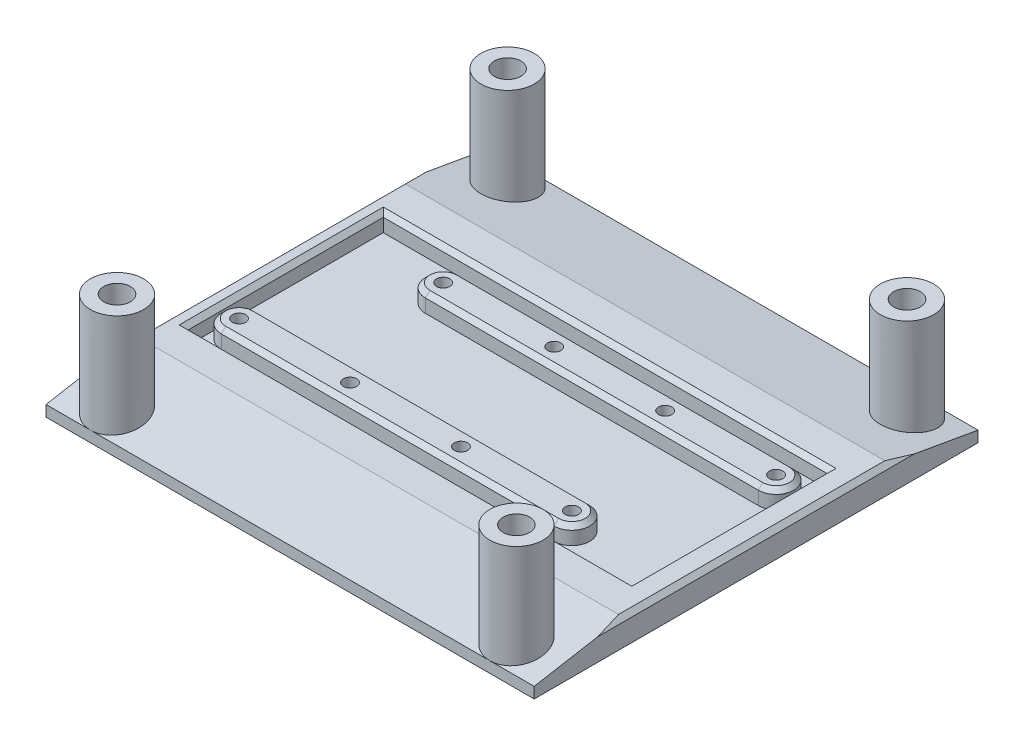
SolidWorks part; units mm, degrees
ref_plane "Спереди" through (0, 0, 0) normal (0, 0, 1) x (1, 0, 0)
ref_plane "Сверху" through (0, 0, 0) normal (0, 1, 0) x (1, 0, 0)
ref_plane "Справа" through (0, 0, 0) normal (1, 0, 0) x (0, 0, -1)
sketch "Эскиз1" plane through (0, 0, 0) normal (0, 1, 0) x (1, 0, 0)
  line L0 (-55, -50) -> (55, -50)
  line L2 (55, -50) -> (55, 50)
  line L3 (55, 50) -> (-55, 50)
  line L4 (-55, 50) -> (-55, -50)
  circle A0 centre (-45, 44) radius 3
  circle A1 centre (-45, -44) radius 3
  circle A2 centre (45, -44) radius 3
  circle A3 centre (45, 44) radius 3
extrude "Бобышка-Вытянуть1" add sketch "Эскиз1" along normal blind 2
ref_plane "Плоскость1" through (0, 2, 0) normal (0, 1, 0) x (1, 0, 0)
sketch "Эскиз2" plane through (0, 2, 0) normal (0, 1, 0) x (1, 0, 0)
  line L0 (-51, 22) -> (-51, -22)
  line L1 (-51, 22) -> (49, 22)
  line L6 (49, -22) -> (49, 22)
  line L11 (-51, -22) -> (49, -22)
  line L12 (55, -50) -> (-55, -50)
  line L13 (-55, -50) -> (-55, 50)
  line L14 (-55, 50) -> (55, 50)
  line L15 (55, -50) -> (55, 50) construction
  line L16 (55, 50) -> (-55, 50) construction
  line L17 (55, 50) -> (55, -50)
  line L18 (-46.5, -19) -> (28.5, -19)
  line L19 (-46.5, -11) -> (28.5, -11)
  line L20 (-30.5, 11) -> (44.5, 11)
  line L21 (-30.5, 19) -> (44.5, 19)
  circle A0 centre (-45, 44) radius 3
  circle A1 centre (45, 44) radius 3
  circle A2 centre (45, -44) radius 3
  circle A3 centre (-45, -44) radius 3
  circle A10 centre (-46.5, -15) radius 1.5
  circle A12 centre (-30.5, 15) radius 1.5
  circle A14 centre (-5.5, 15) radius 1.5
  circle A15 centre (-21.5, -15) radius 1.5
  circle A16 centre (19.5, 15) radius 1.5
  circle A17 centre (3.5, -15) radius 1.5
  circle A18 centre (44.5, 15) radius 1.5
  circle A19 centre (28.5, -15) radius 1.5
  arc A28 (-30.5, 19) -> (-30.5, 11) centre (-30.5, 15) ccw
  arc A29 (44.5, 19) -> (44.5, 11) centre (44.5, 15) cw
  arc A30 (-46.5, -19) -> (-46.5, -11) centre (-46.5, -15) cw
  arc A31 (28.5, -11) -> (28.5, -19) centre (28.5, -15) cw
extrude "Бобышка-Вытянуть2" add sketch "Эскиз2" along normal blind 4 contours L17 L14 L13 L12 A3 A2 A1 A0 L11 L0 L1 L6 | A29 L21 A28 L20 A18 A16 A14 A12 | A31 L19 A30 L18 A10 A15 A17 A19 region at (0, 2, 48.5134) region at (-9, 2, 15) region at (7, 2, -15)
chamfer "Фаска1" distance 1 angle 45 12 edges at (7, 6, -19) (-34.5, 6, -15) (48.5, 6, -15) (7, 6, -11) (-9, 6, 11) (-50.5, 6, 15) (32.5, 6, 15) (-9, 6, 19) (-1, 6, 22) (49, 6, 0) (-51, 6, 0) (-1, 6, -22)
ref_plane "Плоскость2" through (0, 6, 0) normal (0, 1, 0) x (1, 0, 0)
sketch "Эскиз3" plane through (0, 6, 0) normal (0, 1, 0) x (1, 0, 0)
  circle A0 centre (-45, 44) radius 3
  circle A1 centre (45, 44) radius 3
  circle A2 centre (45, -44) radius 3
  circle A3 centre (-45, -44) radius 3
  circle A4 centre (-45, -44) radius 6
  circle A5 centre (45, -44) radius 6
  circle A6 centre (45, 44) radius 6
  circle A7 centre (-45, 44) radius 6
extrude "Бобышка-Вытянуть3" add sketch "Эскиз3" along normal blind 20
chamfer "Фаска2" distance 1 angle 45 2 edges at (-55, 6, 0) (55, 6, 0)
chamfer "Фаска3" distance 20 angle 10 2 edges at (-49.5, 6, -50) (49.5, 6, 50) first distance on face at (-1, 6, 0)
